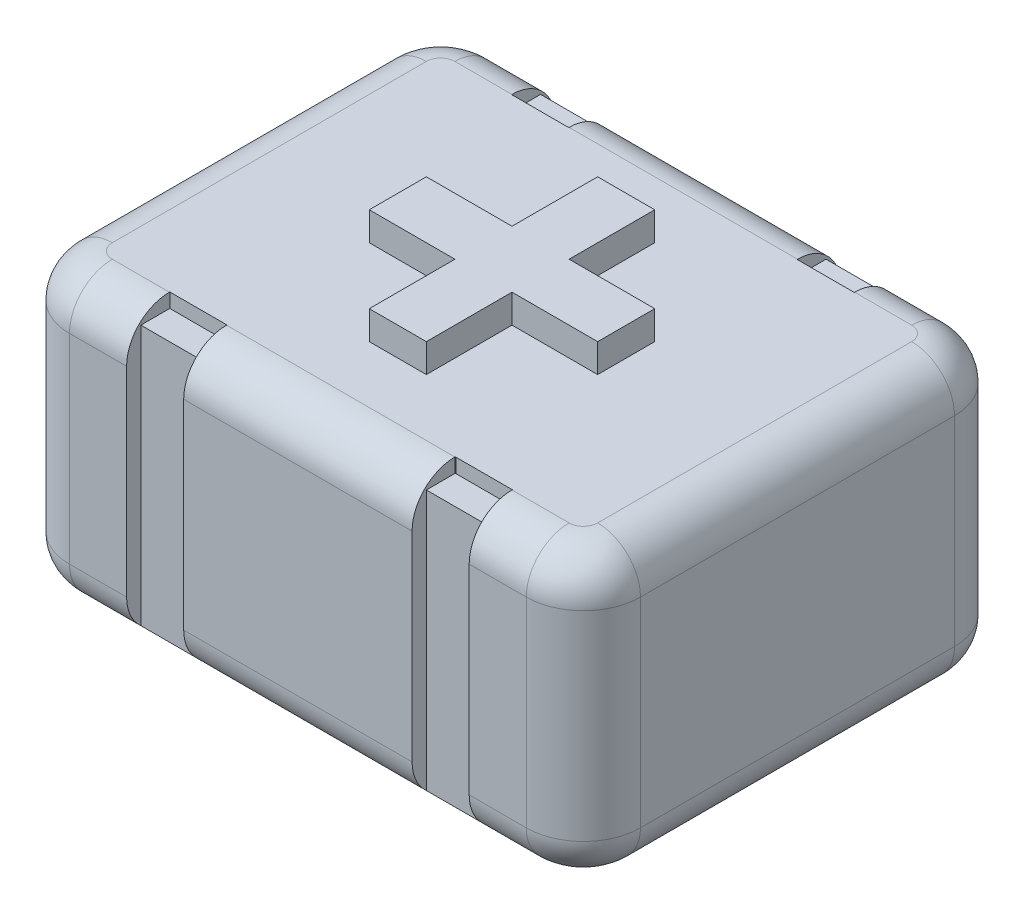
SolidWorks part; units mm, degrees
ref_plane "Front Plane" through (0, 0, 0) normal (0, 0, 1) x (1, 0, 0)
ref_plane "Top Plane" through (0, 0, 0) normal (0, 1, 0) x (1, 0, 0)
ref_plane "Right Plane" through (0, 0, 0) normal (1, 0, 0) x (0, 0, -1)
sketch "Sketch1" plane through (0, 0, 0) normal (0, 1, 0) x (1, 0, 0)
  line L1 (-8, 7.5) -> (8, 7.5)
  line L2 (-10, 5.5) -> (-10, -5.5)
  line L3 (-8, -7.5) -> (8, -7.5)
  line L4 (10, 5.5) -> (10, -5.5)
  line L5 (-10, 7.5) -> (10, -7.5) construction
  line L6 (-10, -7.5) -> (10, 7.5) construction
  arc A0 (8, -7.5) -> (10, -5.5) centre (8, -5.5) ccw
  arc A1 (-8, -7.5) -> (-10, -5.5) centre (-8, -5.5) cw
  arc A2 (10, 5.5) -> (8, 7.5) centre (8, 5.5) ccw
  arc A3 (-8, 7.5) -> (-10, 5.5) centre (-8, 5.5) ccw
  point P0 (0, 0)
  dimension "D4" = 2
  dimension "D1" = 20
  dimension "D2" = 15
  dimension "D3" = 15
extrude "Boss-Extrude1" add sketch "Sketch1" along normal blind 10
sketch "Sketch2" plane through (0, 10, 0) normal (0, 1, 0) x (1, 0, 0)
  line L0 (-6, 7) -> (-6, 7.5)
  line L1 (-6, 7) -> (-4, 7)
  line L2 (-4, 7) -> (-4, 7.5)
  line L3 (8, 7.5) -> (-8, 7.5) construction
  line L4 (-6, 7.5) -> (-4, 7.5)
  line L5 (0, 7.5) -> (0, -7.5) construction
  line L6 (-8, -7.5) -> (8, -7.5) construction
  line L7 (6, 7) -> (6, 7.5)
  line L8 (6, 7) -> (4, 7)
  line L9 (4, 7) -> (4, 7.5)
  line L10 (6, 7.5) -> (4, 7.5)
  line L11 (-10, 5.5) -> (-10, -5.5) construction
  line L12 (-10, 0) -> (10, 0) construction
  line L13 (10, -5.5) -> (10, 5.5) construction
  line L14 (6, -7) -> (4, -7)
  line L15 (4, -7) -> (4, -7.5)
  line L16 (6, -7.5) -> (4, -7.5)
  line L17 (6, -7) -> (6, -7.5)
  line L18 (-6, -7) -> (-6, -7.5)
  line L19 (-6, -7) -> (-4, -7)
  line L20 (-4, -7) -> (-4, -7.5)
  line L21 (-6, -7.5) -> (-4, -7.5)
  dimension "D1" = 2
  dimension "D2" = 0.5
  dimension "D3" = 4
extrude "Cut-Extrude1" cut sketch "Sketch2" against normal blind 10
sketch "Sketch3" plane through (0, 10, 0) normal (0, 1, 0) x (1, 0, 0)
  line L0 (0, 7.5) -> (0, -7.5) construction
  line L2 (-6, 7) -> (-6, 5.9868)
  line L3 (-6, 5.9868) -> (-4.0226, 5.9868)
  line L5 (4, 7.5) -> (-4, 7.5) construction
  line L6 (-4, -7.5) -> (4, -7.5) construction
  line L7 (-10, 0) -> (10, 0) construction
  line L8 (-10, 5.5) -> (-10, -5.5) construction
  line L9 (10, -5.5) -> (10, 5.5) construction
  line L22 (-6, 7) -> (-4, 7)
  line L23 (-4, 7) -> (-4, 6)
  line L24 (-4, 6) -> (-4.0226, 5.9868)
  line L25 (4, 7) -> (4, 6)
  line L26 (6, 7) -> (4, 7)
  line L27 (6, 7) -> (6, 5.9868)
  line L28 (6, 5.9868) -> (4.0226, 5.9868)
  line L29 (4, 6) -> (4.0226, 5.9868)
  line L30 (6, -7) -> (4, -7)
  line L31 (6, -7) -> (6, -5.9868)
  line L32 (6, -5.9868) -> (4.0226, -5.9868)
  line L33 (4, -6) -> (4.0226, -5.9868)
  line L34 (4, -7) -> (4, -6)
  line L35 (-4, -7) -> (-4, -6)
  line L36 (-6, -7) -> (-4, -7)
  line L37 (-6, -7) -> (-6, -5.9868)
  line L38 (-6, -5.9868) -> (-4.0226, -5.9868)
  line L39 (-4, -6) -> (-4.0226, -5.9868)
extrude "Cut-Extrude2" cut sketch "Sketch3" against normal blind 0.5
fillet "Fillet1" radius 1.5 12 edges at (-9.4142, 10, 6.9142) (-10, 10, 0) (-9.4142, 10, -6.9142) (7, 10, -7.5) (-7, 10, -7.5) (9.4142, 10, -6.9142) (10, 10, 0) (9.4142, 10, 6.9142) (7, 10, 7.5) (-7, 10, 7.5) (0, 10, 7.5) (0, 10, -7.5)
fillet "Fillet2" radius 1.5 9 edges at (9.4142, 0, -6.9142) (10, 0, 0) (9.4142, 0, 6.9142) (-9.4142, 0, 6.9142) (-10, 0, 0) (-9.4142, 0, -6.9142) (-7, 0, -7.5) (7, 0, -7.5) (7, 0, 7.5)
sketch "Sketch4" plane through (0, 10, 0) normal (0, 1, 0) x (1, 0, 0)
  line L0 (-8.5, 0) -> (8.5, 0) construction
  line L1 (-1, 4) -> (1, 4)
  line L2 (-1, 4) -> (-1, 1)
  line L3 (-1, -4) -> (1, -4)
  line L4 (1, 4) -> (1, 1)
  line L5 (-8.5, 5.5) -> (-8.5, -5.5) construction
  line L6 (8.5, -5.5) -> (8.5, 5.5) construction
  line L7 (0, 6) -> (0, -6) construction
  line L8 (-4, 1) -> (-1, 1)
  line L9 (-4, 1) -> (-4, -1)
  line L10 (-4, -1) -> (-1, -1)
  line L11 (4, 1) -> (4, -1)
  line L12 (4, 6) -> (-4, 6) construction
  line L13 (-4, -6) -> (4, -6) construction
  line L14 (-1, -1) -> (-1, -4)
  line L15 (1, -1) -> (1, -4)
  line L16 (1, 1) -> (4, 1)
  line L17 (1, -1) -> (4, -1)
  dimension "D1" = 2
  dimension "D2" = 8
  dimension "D3" = 4
  dimension "D4" = 8
  dimension "D5" = 2
  dimension "D6" = 4
  dimension "D7" = 1
  dimension "D8" = 1
  dimension "D9" = 3
  dimension "D10" = 3
  dimension "D11" = 3
  dimension "D12" = 3
  dimension "D13" = 3
  dimension "D14" = 3
extrude "Boss-Extrude2" add sketch "Sketch4" along normal blind 1
